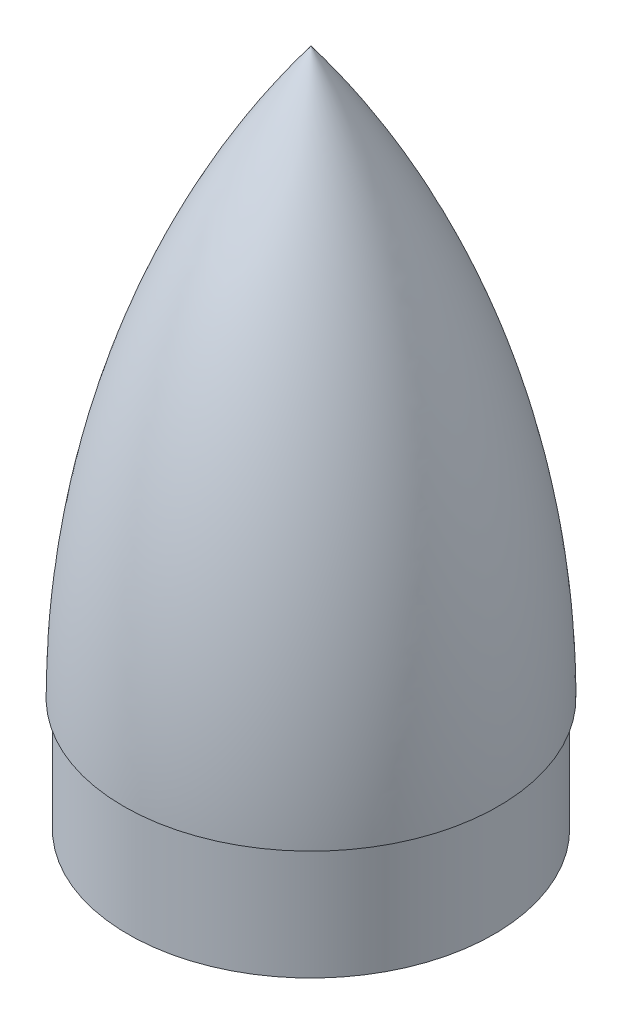
SolidWorks part; units mm, degrees
ref_plane "Front Plane" through (0, 0, 0) normal (0, 0, 1) x (1, 0, 0)
ref_plane "Top Plane" through (0, 0, 0) normal (0, 1, 0) x (1, 0, 0)
ref_plane "Right Plane" through (0, 0, 0) normal (1, 0, 0) x (0, 0, -1)
sketch "Sketch1" plane through (0, 0, 0) normal (0, 0, 1) x (1, 0, 0)
  line L2 (32.385, -20) -> (32.385, 0)
  line L3 (32.385, 0) -> (33.16, 0)
  line L4 (27.385, -20) -> (27.385, 7.8298)
  line L5 (32.385, -20) -> (27.385, -20)
  line L6 (0, 85) -> (0, 100)
  line L7 (26.5421, 24.1638) -> (22.799, 42.8866) construction
  line L8 (35.8939, 2.8907) -> (28.2882, 40.9346) construction
  line L9 (25.0095, 31.8299) -> (29.9124, 32.8101) construction
  arc A0 (0, 100) -> (33.16, 0) centre (-134.2041, 0) cw
  arc A1 (27.385, 7.8298) -> (0, 85) centre (-95.0392, 7.8298) ccw
  point P16 (27.385, 28.736)
  point P17 (26.6849, 20.8484)
  dimension "D1" = 100
  dimension "D2" = 5
  dimension "D3" = 20
  dimension "D4" = 32.385
  dimension "D5" = 33.16
  dimension "D6" = 15
  dimension "D7" = 5
revolve "Revolve1" add sketch "Sketch1" angle 360 about L6
